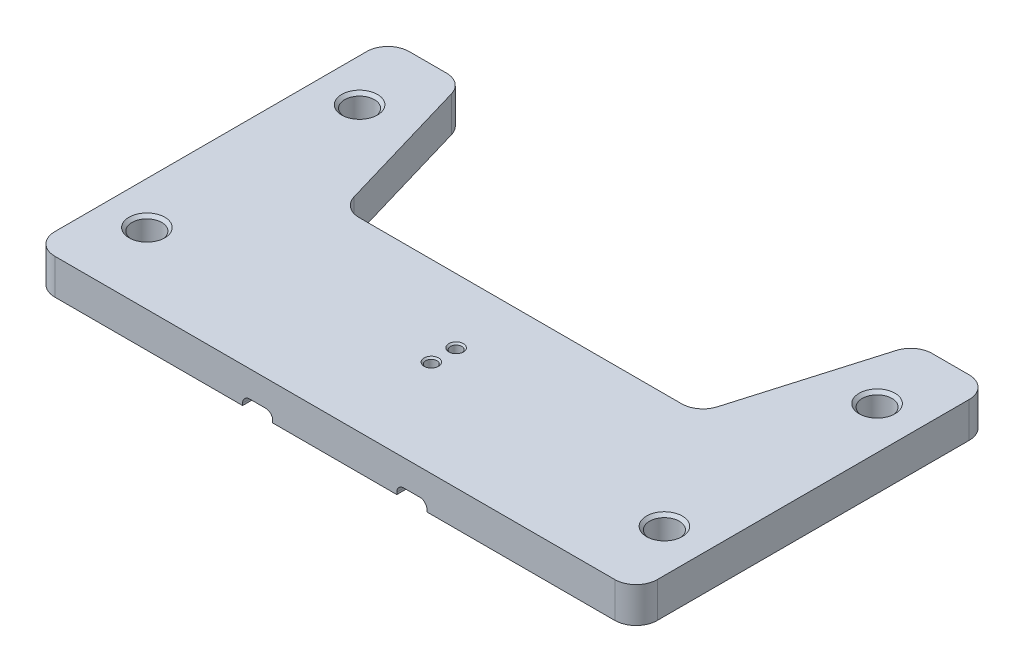
SolidWorks part; units mm, degrees
ref_plane "Front Plane" through (0, 0, 0) normal (0, 0, 1) x (1, 0, 0)
ref_plane "Top Plane" through (0, 0, 0) normal (0, 1, 0) x (1, 0, 0)
ref_plane "Right Plane" through (0, 0, 0) normal (1, 0, 0) x (0, 0, -1)
sketch "Sketch2" plane through (0, 0, 0) normal (0, 1, 0) x (1, 0, 0)
  line L1 (42.5, 0) -> (42.5, 50)
  line L2 (42.5, 50) -> (22.5, 50)
  line L3 (22.5, 50) -> (8.75, 26.1843)
  line L4 (8.75, 26.1843) -> (-8.75, 26.1843)
  line L5 (-8.75, 26.1843) -> (-22.5, 50)
  line L6 (-22.5, 50) -> (-42.5, 50)
  line L7 (-42.5, 50) -> (-42.5, 0)
  line L9 (-42.5, 0) -> (42.5, 0)
  point P0 (0, 26.1843)
  point P3 (0, 0)
  point P11 (32.5, 50)
  point P13 (-32.5, 50)
  dimension "D1" = 17.5
  dimension "D2" = 85
  dimension "D3" = 50
  dimension "D4" = 60
  dimension "D5" = 60
  dimension "D6" = 20
extrude "Boss-Extrude1" add sketch "Sketch2" along normal blind 5
sketch "Sketch3" plane through (0, 0, -26.1843) normal (0, 0, -1) x (-1, 0, 0)
  line L6 (-8.75, 0) -> (8.75, 0)
  line L7 (-8.75, 0) -> (-8.75, 1)
  line L8 (-8.75, 1) -> (8.75, 1)
  line L9 (8.75, 0) -> (8.75, 1)
  point P5 (0, 0)
  dimension "D1" = 17.5
  dimension "D2" = 1
extrude "Cut-Extrude1" [suppressed] cut sketch "Sketch3" against normal through all
hole_wizard "M2x0.4 Tapped Hole1" positions "Sketch4" profile "Sketch5" tap size "M2x0.4" standard "ANSI Metric"
sketch "Sketch4" plane through (0, 5, 0) normal (0, 1, 0) x (1, 0, 0)
  line L0 (-42.5, 0) -> (42.5, 0) construction
  point P0 (0, 13.62)
  point P2 (0, 17.12)
  dimension "D1" = 13.62
  dimension "D2" = 17.12
  dimension "D3" = 8.75
sketch "Sketch5" plane through (0, 5, -13.62) normal (1, 0, 0) x (0, 0, 1)
  line L0 (0, 0) -> (0, 7.7507)
  line L1 (0, 7.7507) -> (0.8, 7.27)
  line L2 (0.8, 7.27) -> (0.8, 0.225)
  line L3 (0.8, 0.225) -> (1.025, 0)
  line L5 (1.025, 0) -> (0, 0)
  line L6 (-0.8, 0.225) -> (-1.025, 0) construction
  line L10 (0, 7.7507) -> (-0.8, 7.27) construction
  line L11 (0, -6.35) -> (0, 107.95) construction
  dimension "Tap Drill Dia." = 1.6
  dimension "Tap Drill Depth" = 7.27
  dimension "Near C'Sink Dia." = 2.05
  dimension "Near C'Sink Angle" = 90
  dimension "Drill Angle" = 118
cosmetic thread "Hole Thread1" parameters "D1"=6.07, "D2"=2
cosmetic thread "Hole Thread2" parameters "D1"=6.07, "D2"=2
hole_wizard "M5x0.8 Tapped Hole1" positions "Sketch6" profile "Sketch7" tap size "M5x0.8" standard "ANSI Metric"
sketch "Sketch6" plane through (0, 5, 0) normal (0, 1, 0) x (1, 0, 0)
  line L1 (-22.5, 50) -> (-42.5, 50) construction
  line L2 (42.5, 50) -> (22.5, 50) construction
  line L3 (42.5, 0) -> (42.5, 50) construction
  line L4 (-42.5, 50) -> (-42.5, 0) construction
  line L5 (-42.5, 0) -> (42.5, 0) construction
  point P0 (-36.5, 40)
  point P2 (36.5, 40)
  point P18 (-36.5, 10)
  point P20 (36.5, 10)
  dimension "D1" = 6
  dimension "D2" = 10
  dimension "D3" = 10
  dimension "D4" = 6
  dimension "D5" = 10
  dimension "D6" = 10
sketch "Sketch7" plane through (-36.5, 5, -40) normal (1, 0, 0) x (0, 0, 1)
  line L0 (0, 0) -> (0, 13.6618)
  line L1 (0, 13.6618) -> (2.1, 12.4)
  line L2 (2.1, 12.4) -> (2.1, 0.425)
  line L3 (2.1, 0.425) -> (2.525, 0)
  line L5 (2.525, 0) -> (0, 0)
  line L6 (-2.1, 0.425) -> (-2.525, 0) construction
  line L10 (0, 13.6618) -> (-2.1, 12.4) construction
  line L11 (0, -6.35) -> (0, 107.95) construction
  dimension "Tap Drill Dia." = 4.2
  dimension "Tap Drill Depth" = 12.4
  dimension "Near C'Sink Dia." = 5.05
  dimension "Near C'Sink Angle" = 90
  dimension "Drill Angle" = 118
cosmetic thread "Hole Thread3" parameters "D1"=10, "D2"=5
cosmetic thread "Hole Thread4" parameters "D1"=10, "D2"=5
cosmetic thread "Hole Thread5" parameters "D1"=10, "D2"=5
cosmetic thread "Hole Thread6" parameters "D1"=10, "D2"=5
sketch "Sketch8" plane through (0, 0, -26.1843) normal (0, 0, -1) x (-1, 0, 0)
  line L5 (-8.75, 5) -> (-8.75, 0) construction
  line L6 (-13, 0) -> (-8.75, 0)
  line L7 (-13, 0) -> (-13, 1.3)
  line L8 (-13, 1.3) -> (-8.75, 1.3)
  line L9 (-8.75, 0) -> (-8.75, 1.3)
  line L10 (0, 0) -> (0, 12.6228) construction
  line L11 (8.75, 0) -> (8.75, 1.3)
  line L12 (13, 1.3) -> (8.75, 1.3)
  line L13 (13, 0) -> (13, 1.3)
  line L14 (13, 0) -> (8.75, 0)
  line L15 (-22.5, 0) -> (-8.75, 0) construction
  dimension "D1" = 4.25
  dimension "D2" = 1.3
extrude "Cut-Extrude2" cut sketch "Sketch8" against normal through all both and the other way through all
sketch "Sketch9" plane through (0, 0, 0) normal (0, -1, 0) x (1, 0, 0)
  line L0 (-32, -50) -> (-25, -26.1843)
  line L1 (-22.5, -50) -> (-42.5, -50) construction
  line L3 (25, -26.1843) -> (32, -50)
  line L4 (42.5, -50) -> (22.5, -50) construction
  line L5 (32, -50) -> (-32, -50)
  line L6 (-25, -26.1843) -> (25, -26.1843)
  line L7 (8.75, -26.1843) -> (-8.75, -26.1843) construction
  point P8 (0, -50)
  point P12 (0, -26.1843)
  dimension "D1" = 64
  dimension "D2" = 50
extrude "Cut-Extrude3" cut sketch "Sketch9" against normal through all
fillet "Fillet1" radius 3 8 edges at (42.5, 2.5, -50) (-42.5, 2.5, -50) (-32, 2.5, -50) (32, 2.5, -50) (25, 2.5, -26.1843) (-25, 2.5, -26.1843) (42.5, 2.5, 0) (-42.5, 2.5, 0)
fillet "Fillet2" radius 1 4 edges at (-13, 1.3, -13.0922) (-8.75, 1.3, -13.0922) (8.75, 1.3, -13.0922) (13, 1.3, -13.0922)
